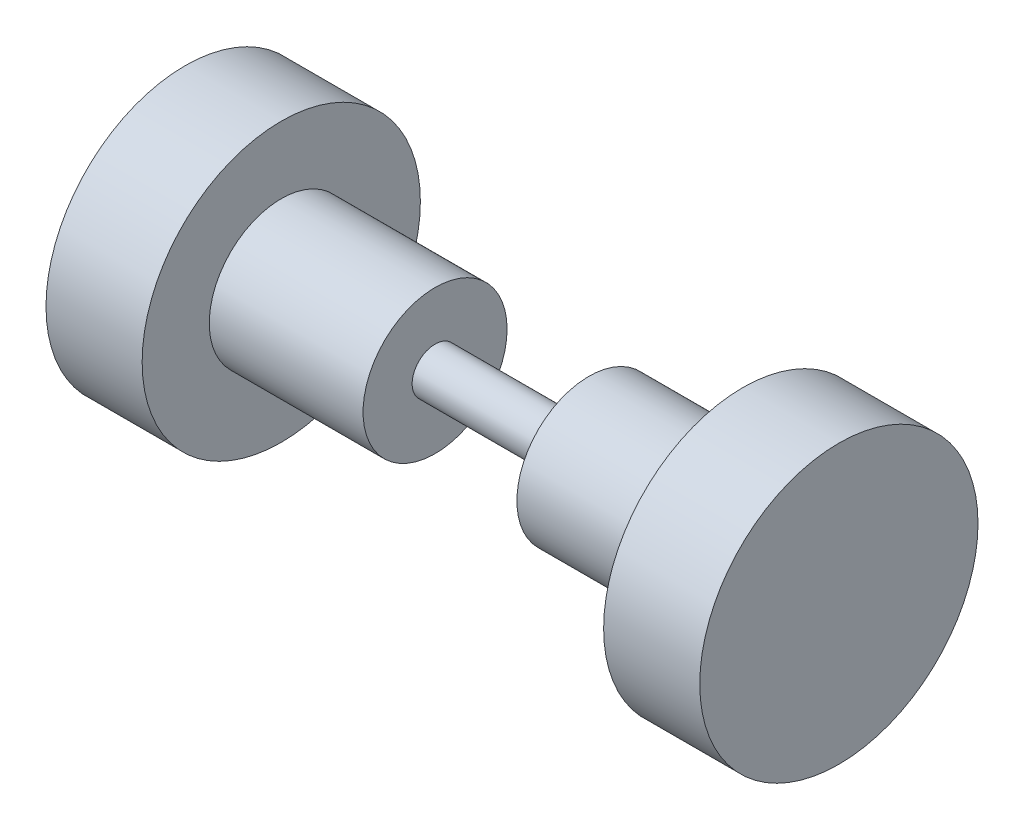
SolidWorks part; units mm, degrees
ref_plane "Front Plane" through (0, 0, 0) normal (0, 0, 1) x (1, 0, 0)
ref_plane "Top Plane" through (0, 0, 0) normal (0, 1, 0) x (1, 0, 0)
ref_plane "Right Plane" through (0, 0, 0) normal (1, 0, 0) x (0, 0, -1)
sketch "Sketch1" plane through (0, 0, 0) normal (0, 1, 0) x (1, 0, 0)
  line L0 (-6.096, 1.9024) -> (-2.032, 1.9024)
  line L1 (-2.032, 1.9024) -> (-2.032, 0.6065)
  line L2 (-2.032, 0.6065) -> (2.032, 0.6065)
  line L3 (2.032, 0.6065) -> (2.032, 1.9024)
  line L4 (2.032, 1.9024) -> (6.096, 1.9024)
  line L5 (6.096, 1.9024) -> (6.096, 3.6752)
  line L6 (6.096, 3.6752) -> (8.636, 3.6752)
  line L7 (8.636, 3.6752) -> (8.636, 0)
  line L8 (8.636, 0) -> (-8.636, 0)
  line L9 (-8.636, 0) -> (-8.636, 3.6752)
  line L10 (-8.636, 3.6752) -> (-6.096, 3.6752)
  line L11 (-6.096, 3.6752) -> (-6.096, 1.9024)
  point P12 (0, 0.6065)
  dimension "D1" = 4.064
  dimension "D2" = 4.064
  dimension "D3" = 2.54
revolve "Revolve1" add sketch "Sketch1" angle 360 about L8
